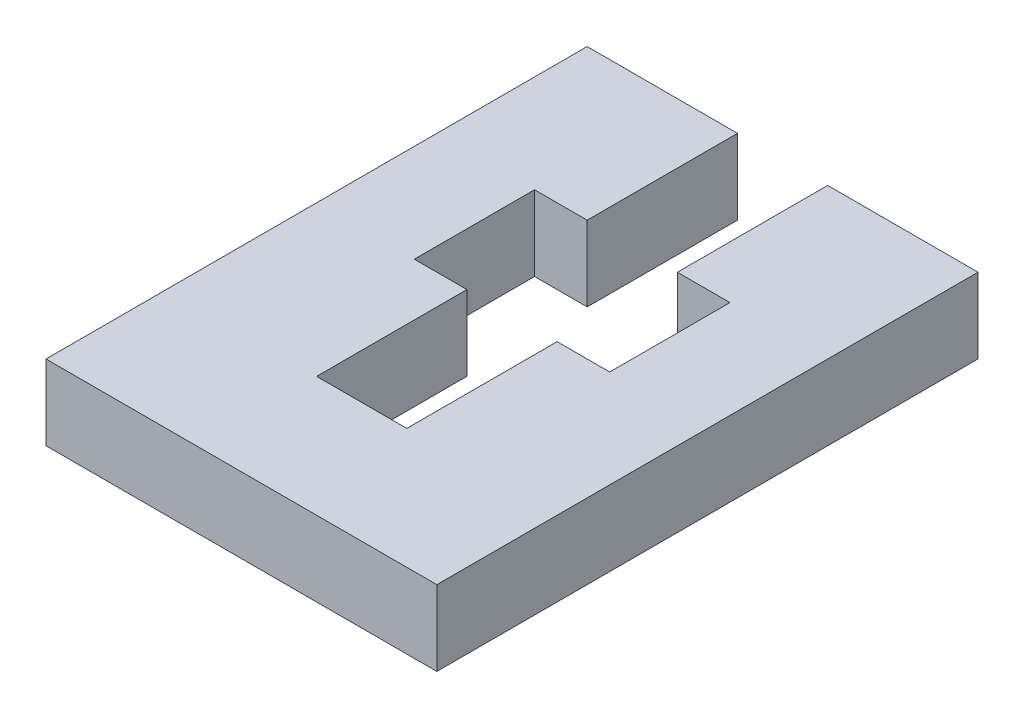
SolidWorks part; units mm, degrees
ref_plane "Front Plane" through (0, 0, 0) normal (0, 0, 1) x (1, 0, 0)
ref_plane "Top Plane" through (0, 0, 0) normal (0, 1, 0) x (1, 0, 0)
ref_plane "Right Plane" through (0, 0, 0) normal (1, 0, 0) x (0, 0, -1)
sketch "Sketch1" plane through (0, 0, 0) normal (0, 1, 0) x (1, 0, 0)
  line L0 (1.5, 8.5) -> (1.5, 3.5)
  line L1 (1.5, 3.5) -> (3.25, 3.5)
  line L2 (3.25, 3.5) -> (3.25, -0.5)
  line L3 (3.25, -0.5) -> (1.5, -0.5)
  line L4 (1.5, -0.5) -> (1.5, -5.5)
  line L5 (1.5, -5.5) -> (-1.5, -5.5)
  line L6 (-1.5, -5.5) -> (-1.5, -0.5)
  line L7 (-1.5, -0.5) -> (-3.25, -0.5)
  line L8 (-3.25, -0.5) -> (-3.25, 3.5)
  line L9 (-3.25, 3.5) -> (-1.5, 3.5)
  line L10 (-1.5, 3.5) -> (-1.5, 8.5)
  line L12 (-1.5, 8.5) -> (-6.5, 8.5)
  line L13 (-6.5, 8.5) -> (-6.5, -9.5)
  line L14 (-6.5, -9.5) -> (6.5, -9.5)
  line L15 (6.5, -9.5) -> (6.5, 8.5)
  line L16 (6.5, 8.5) -> (1.5, 8.5)
  point P0 (0, -5.5)
  point P17 (0, -9.5)
  dimension "D1" = 5
  dimension "D2" = 4
  dimension "D3" = 1.75
  dimension "D4" = 1.75
  dimension "D5" = 5
  dimension "D6" = 3
  dimension "D7" = 5
  dimension "D8" = 4
extrude "Boss-Extrude1" add sketch "Sketch1" along normal blind 2.5
